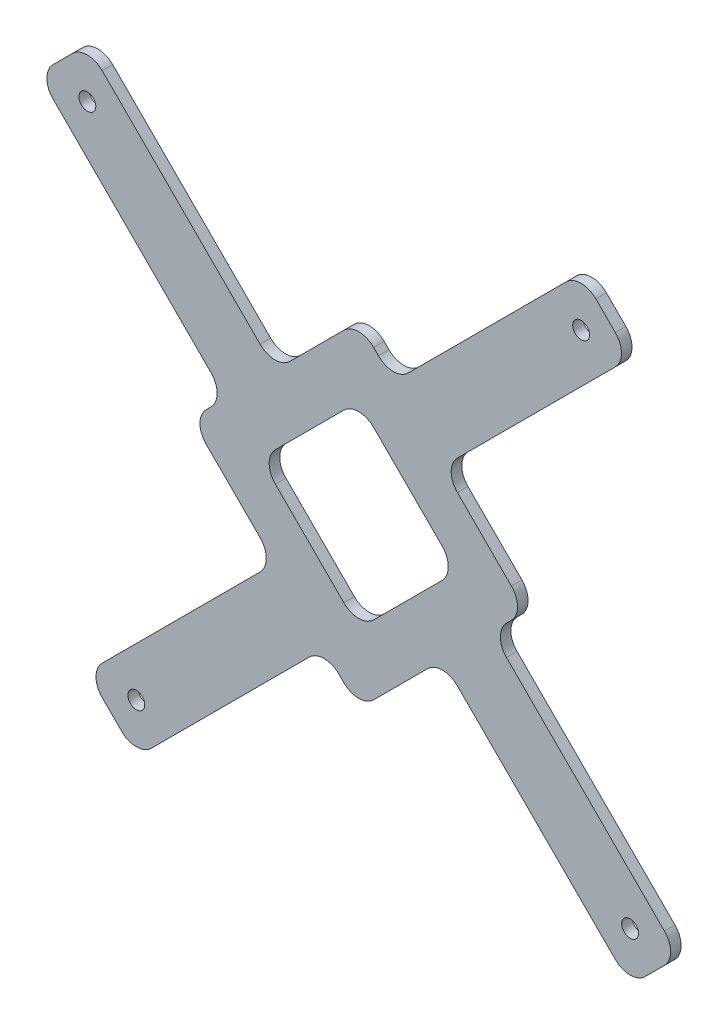
SolidWorks part; units mm, degrees
ref_plane "Front Plane" through (0, 0, 0) normal (0, 0, 1) x (1, 0, 0)
ref_plane "Top Plane" through (0, 0, 0) normal (0, 1, 0) x (1, 0, 0)
ref_plane "Right Plane" through (0, 0, 0) normal (1, 0, 0) x (0, 0, -1)
sketch "Sketch2" plane through (0, 0, 70.5078) normal (0, 0, -1) x (-1, 0, 0)
  line L0 (-109.4917, -65.7542) -> (-99.2387, -55.5012)
  line L1 (-77.6719, -39.5913) -> (-67.4189, -49.8443)
  line L2 (-51.509, -71.4111) -> (-61.762, -81.6641)
  line L3 (-83.3288, -97.574) -> (-93.5818, -87.321)
  line L4 (-129.2412, -19.8419) -> (-99.2387, -49.8443)
  line L5 (-129.2412, -14.185) -> (-125.5642, -10.508)
  line L6 (-119.9074, -10.508) -> (-89.9049, -40.5105)
  line L7 (-61.762, -49.8443) -> (-31.7595, -19.8419)
  line L8 (-26.1027, -19.8419) -> (-22.4257, -23.5188)
  line L9 (-22.4257, -29.1757) -> (-52.4282, -59.1781)
  line L10 (-41.0934, -126.6573) -> (-71.0958, -96.6548)
  line L11 (-31.7595, -122.9803) -> (-35.4365, -126.6573)
  line L12 (-31.7595, -117.3235) -> (-61.762, -87.321)
  line L13 (-99.2387, -87.321) -> (-129.2412, -117.3235)
  line L14 (-134.898, -117.3235) -> (-138.575, -113.6465)
  line L15 (-138.575, -107.9897) -> (-108.5725, -77.9872)
  line L16 (-108.5725, -72.3303) -> (-109.4917, -71.4111)
  line L17 (-84.248, -40.5105) -> (-83.3288, -39.5913)
  line L18 (-52.4282, -64.835) -> (-51.509, -65.7542)
  line L19 (-76.7527, -96.6548) -> (-77.6719, -97.574)
  line L20 (-96.3395, -65.7542) -> (-83.3288, -52.7435)
  line L21 (-77.6719, -52.7435) -> (-64.6612, -65.7542)
  line L22 (-64.6612, -71.4111) -> (-77.6719, -84.4219)
  line L23 (-83.3288, -84.4219) -> (-96.3395, -71.4111)
  circle A0 centre (-132.055, -110.8327) radius 1.6
  circle A1 centre (-28.9457, -26.3327) radius 1.6
  circle A2 centre (-122.7504, -17.028) radius 1.6
  circle A3 centre (-38.2504, -120.1373) radius 1.6
  arc A4 (-64.6612, -65.7542) -> (-64.6612, -71.4111) centre (-67.4896, -68.5827) cw
  arc A5 (-83.3288, -52.7435) -> (-77.6719, -52.7435) centre (-80.5004, -55.5719) cw
  arc A6 (-96.3395, -71.4111) -> (-96.3395, -65.7542) centre (-93.5111, -68.5827) cw
  arc A7 (-77.6719, -84.4219) -> (-83.3288, -84.4219) centre (-80.5004, -81.5934) cw
  arc A8 (-125.5642, -10.508) -> (-119.9074, -10.508) centre (-122.7358, -13.3365) cw
  arc A9 (-129.2412, -19.8419) -> (-129.2412, -14.185) centre (-126.4127, -17.0134) cw
  arc A10 (-71.0958, -96.6548) -> (-76.7527, -96.6548) centre (-73.9243, -99.4832) ccw
  arc A11 (-61.762, -87.321) -> (-61.762, -81.6641) centre (-58.9336, -84.4926) cw
  arc A12 (-51.509, -65.7542) -> (-51.509, -71.4111) centre (-54.3374, -68.5827) cw
  arc A13 (-52.4282, -59.1781) -> (-52.4282, -64.835) centre (-49.5998, -62.0066) ccw
  arc A14 (-31.7595, -19.8419) -> (-26.1027, -19.8419) centre (-28.9311, -22.6703) cw
  arc A15 (-22.4257, -23.5188) -> (-22.4257, -29.1757) centre (-25.2542, -26.3472) cw
  arc A16 (-61.762, -49.8443) -> (-67.4189, -49.8443) centre (-64.5905, -47.0159) cw
  arc A17 (-83.3288, -39.5913) -> (-77.6719, -39.5913) centre (-80.5004, -42.4197) cw
  arc A18 (-89.9049, -40.5105) -> (-84.248, -40.5105) centre (-87.0765, -37.6821) ccw
  arc A19 (-99.2387, -49.8443) -> (-99.2387, -55.5012) centre (-102.0671, -52.6728) cw
  arc A20 (-99.2387, -87.321) -> (-93.5818, -87.321) centre (-96.4103, -90.1494) cw
  arc A21 (-108.5725, -77.9872) -> (-108.5725, -72.3303) centre (-111.4009, -75.1588) ccw
  arc A22 (-109.4917, -65.7542) -> (-109.4917, -71.4111) centre (-106.6633, -68.5827) ccw
  arc A23 (-31.7595, -117.3235) -> (-31.7595, -122.9803) centre (-34.588, -120.1519) cw
  arc A24 (-35.4365, -126.6573) -> (-41.0934, -126.6573) centre (-38.2649, -123.8289) cw
  arc A25 (-77.6719, -97.574) -> (-83.3288, -97.574) centre (-80.5004, -94.7456) cw
  arc A26 (-129.2412, -117.3235) -> (-134.898, -117.3235) centre (-132.0696, -114.495) cw
  arc A27 (-138.575, -113.6465) -> (-138.575, -107.9897) centre (-135.7466, -110.8181) cw
  point P6 (-122.7504, -17.028)
  point P25 (-80.5004, -68.5827)
  point P48 (-73.9243, -93.8264)
  point P59 (-55.2566, -62.0066)
  point P66 (-87.0765, -43.339)
  point P77 (-105.7441, -75.1588)
  dimension "D6" = 6.6
  dimension "D9" = 22.5
  dimension "D21" = 4
  dimension "D1" = 145.8598
  dimension "D2" = 145.8598
  dimension "D3" = 72.9299
  dimension "D4" = 72.9299
  dimension "D5" = 6.6
  dimension "D7" = 6.6
  dimension "D8" = 6.6
  dimension "D10" = 3.6915
  dimension "D11" = 3.6624
  dimension "D12" = 3.6916
  dimension "D13" = 3.6624
  dimension "D14" = 3.6915
  dimension "D15" = 3.6624
  dimension "D16" = 3.6624
  dimension "D17" = 3.6915
  dimension "D18" = 22.5
  dimension "D19" = 22.5
  dimension "D20" = 22.5
extrude "Boss-Extrude1" add sketch "Sketch2" along normal blind 2
ref_axis "Axis1" through (132.055, -110.8327, 70.5078) along (0, 0, -1)
ref_axis "Axis2" through (28.9457, -26.3327, 70.5078) along (0, 0, -1)
